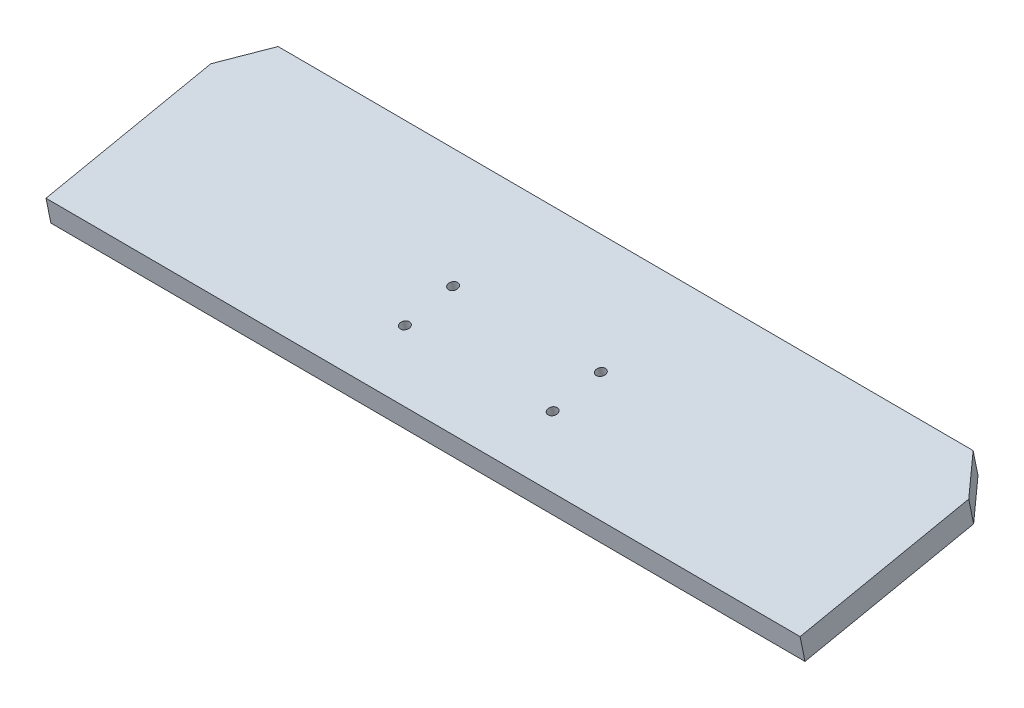
SolidWorks part; units mm, degrees
material "Plain Carbon Steel"
ref_plane "Front Plane" through (0, 0, 0) normal (0, 0, 1) x (1, 0, 0)
ref_plane "Top Plane" through (0, 0, 0) normal (0, 1, 0) x (1, 0, 0)
ref_plane "Right Plane" through (0, 0, 0) normal (1, 0, 0) x (0, 0, -1)
ref_axis "Centerline" through (0, 192.8789, -174.9002) along (0, -0.2021, 0.9794)
sketch "Sketch2" plane through (0.6833, 150.3852, 31.0298) normal (0.0045, 0.9794, 0.2021) x (-1, 0.0044, 0.0009)
  line L0 (-88.4223, 329.6639) -> (90.8089, 329.6639)
  line L1 (-96.7115, 339.2857) -> (-88.4223, 329.6639)
  line L3 (97.7546, 383.7357) -> (97.7546, 340.2962)
  line L4 (97.7546, 340.2962) -> (90.8089, 329.6639)
  line L10 (-96.7115, 383.7357) -> (-96.7115, 339.2857)
  line L11 (-96.7115, 383.7357) -> (97.7546, 383.7357)
  dimension "D1" = 12.7
extrude "Boss-Extrude1" add sketch "Sketch2" along normal blind 6.35
sketch "Sketch4" plane through (0.7116, 156.6041, 32.313) normal (0.0045, 0.9794, 0.2021) x (1, -0.0044, -0.0009)
  line L0 (-97.7546, -362.016) -> (96.7115, -362.016) construction
  line L1 (-97.7546, -340.2962) -> (-97.7546, -383.7357) construction
  line L2 (96.7115, -383.7357) -> (96.7115, -339.2857) construction
  line L3 (-1.1933, -329.6639) -> (-1.1933, -383.7357) construction
  line L4 (88.4223, -329.6639) -> (-90.8089, -329.6639) construction
  line L5 (-97.7546, -383.7357) -> (96.7115, -383.7357) construction
  circle A0 centre (17.8567, -355.666) radius 1.1906
  circle A1 centre (17.8567, -368.366) radius 1.1906
  circle A2 centre (-20.2433, -368.366) radius 1.1906
  circle A3 centre (-20.2433, -355.666) radius 1.1906
  dimension "D1" = 2.3813
  dimension "D2" = 6.35
  dimension "D3" = 19.05
extrude "Cut-Extrude2" cut sketch "Sketch4" against normal through all
